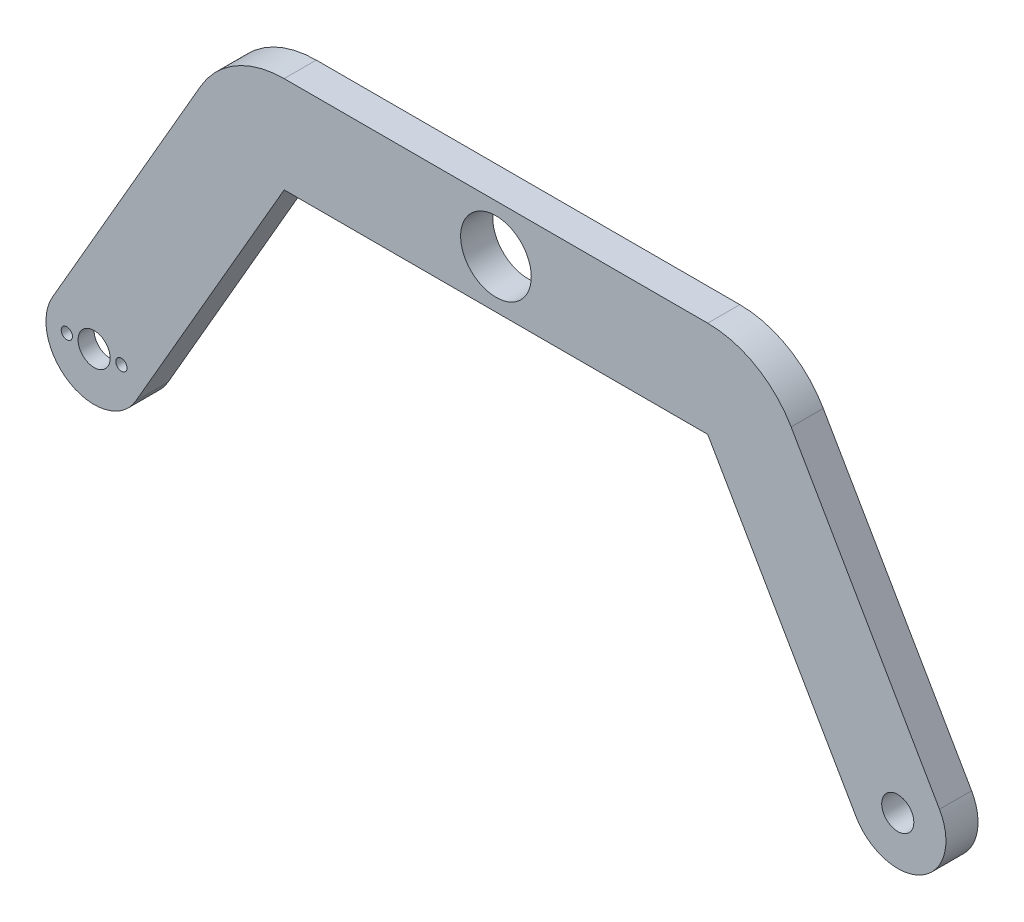
SolidWorks part; units mm, degrees
ref_plane "Front Plane" through (0, 0, 0) normal (0, 0, 1) x (1, 0, 0)
ref_plane "Top Plane" through (0, 0, 0) normal (0, 1, 0) x (1, 0, 0)
ref_plane "Right Plane" through (0, 0, 0) normal (1, 0, 0) x (0, 0, -1)
sketch "Sketch1" plane through (0, 0, 0) normal (0, 0, 1) x (1, 0, 0)
  line L0 (0, -15) -> (0, 15) construction
  line L1 (65.9559, 15) -> (-65.9559, 15)
  line L2 (65.9559, -15) -> (-65.9559, -15)
  line L3 (-65.9559, -15) -> (-112.1545, -95.0183)
  line L5 (-138.1353, -80.0183) -> (-91.9367, 0)
  line L6 (138.1353, -80.0183) -> (91.9367, 0)
  line L8 (65.9559, -15) -> (112.1545, -95.0183)
  arc A1 (-91.9367, 0) -> (-65.9559, 15) centre (-65.9559, -15) cw
  arc A2 (91.9367, 0) -> (65.9559, 15) centre (65.9559, -15) ccw
  circle A3 centre (-125.1449, -87.5183) radius 15 construction
  arc A5 (-138.1353, -80.0183) -> (-112.1545, -95.0183) centre (-125.1449, -87.5183) ccw
  arc A6 (112.1545, -95.0183) -> (138.1353, -80.0183) centre (125.1449, -87.5183) ccw
  circle A7 centre (-133.6449, -87.5183) radius 1.75
  circle A8 centre (-116.6449, -87.5183) radius 1.75
  point P4 (0, 0)
  point P6 (0, 15)
  point P10 (0, -15)
  dimension "D2" = 3.5
  dimension "D4" = 3.5
  dimension "D1" = 30
  dimension "D3" = 120
extrude "Boss-Extrude1" add sketch "Sketch1" along normal blind 10
sketch "Sketch2" plane through (0, 0, 10) normal (0, 0, 1) x (1, 0, 0)
  circle A0 centre (0, 0) radius 11
  circle A1 centre (-125.1449, -87.5183) radius 5
  circle A2 centre (125.1449, -87.5183) radius 5
  dimension "D1" = 22
extrude "Cut-Extrude1" cut sketch "Sketch2" against normal up to surface (10 mm away) up to face at (-131.8949, -87.5183, 0)
sketch "Sketch3" plane through (0, 0, 0) normal (0, 0, -1) x (-1, 0, 0)
  circle A0 centre (0, 0) radius 12
sketch "Sketch4" plane through (0, 0, 0) normal (0, 0, -1) x (-1, 0, 0)
  circle A0 centre (125.1449, -87.5183) radius 13
  dimension "D1" = 26
extrude "Cut-Extrude2" cut sketch "Sketch4" against normal offset from surface (5 mm away) 5 up to face at (11, 0, 10)
sketch "Sketch5" plane through (0, 0, 10) normal (0, 0, 1) x (1, 0, 0)
  circle A0 centre (0, 0) radius 3.5
  dimension "D1" = 7
